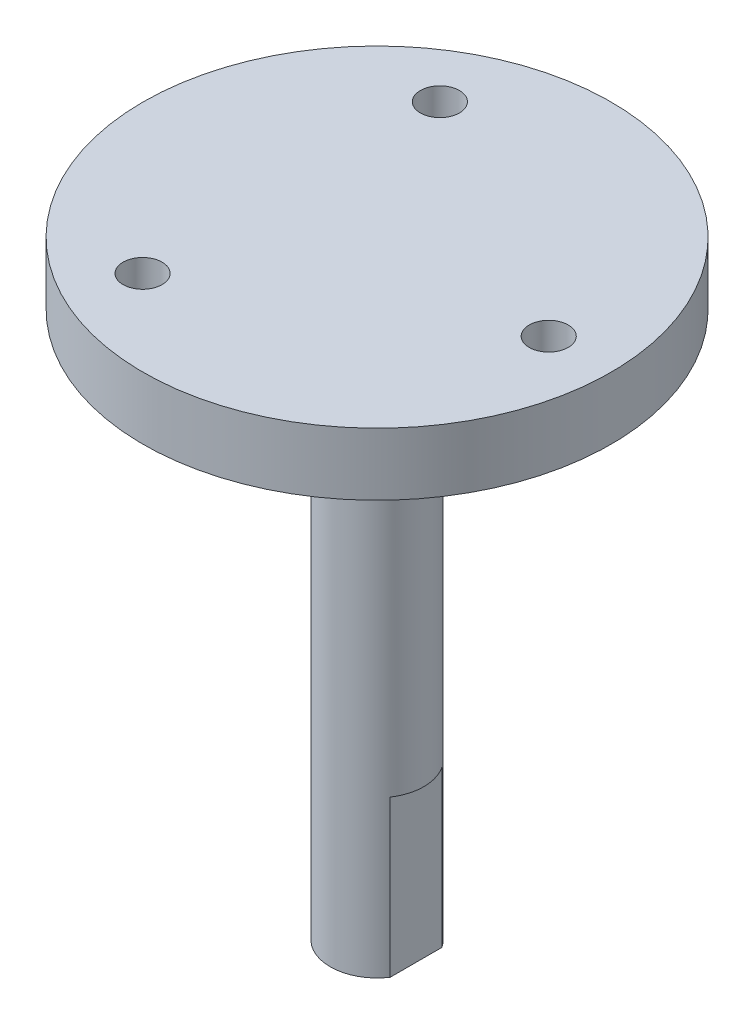
SolidWorks part; units mm, degrees
ref_plane "Alzado" through (0, 0, 0) normal (0, 0, 1) x (1, 0, 0)
ref_plane "Planta" through (0, 0, 0) normal (0, 1, 0) x (1, 0, 0)
ref_plane "Vista lateral" through (0, 0, 0) normal (1, 0, 0) x (0, 0, -1)
sketch "Croquis1" plane through (0, 0, 0) normal (0, 0, 1) x (1, 0, 0)
  line L0 (0, 0) -> (3, 0)
  line L5 (3, 0) -> (3, -39)
  line L6 (3, -39) -> (0, -39)
  line L7 (0, -39) -> (0, 0)
  line L8 (0, -39) -> (0, 5.7552) construction
  dimension "D3" = 39
  dimension "D7" = 6
revolve "Revolución1" add sketch "Croquis1" angle 360 about L8 region at (1.5, -19.5, 0)
sketch "Croquis2" plane through (0, -39, 0) normal (0, -1, 0) x (1, 0, 0)
  line L0 (2.5, 1.6583) -> (2.5, -1.6583)
  line L1 (0, 0) -> (3, 0) construction
  circle A0 centre (0, 0) radius 3
  circle A1 centre (0, 0) radius 3
  circle M3 centre (0, 0) radius 3
  dimension "D1" = 0.5
extrude "Cortar-Extruir1" cut sketch "Croquis2" against normal blind 10 contours L1 L0 M3 | L0 L1 A1 region at (2.7015, -39, 0.6294) region at (2.7015, -39, -0.6294)
sketch "Croquis4" plane through (0, 0, 0) normal (0, 1, 0) x (1, 0, 0)
  circle A2 centre (0, 0) radius 15
  dimension "D1" = 30
extrude "Saliente-Extruir1" add sketch "Croquis4" against normal blind 4
sketch "Croquis5" plane through (0, 0, 0) normal (0, 1, 0) x (1, 0, 0)
  line L0 (0, 0) -> (11, 0) construction
  point P0 (11, 0)
  point P5 (-5.5, -9.5263)
  point P8 (-5.5, 9.5263)
  point P9 (0, 0)
  dimension "D1" = 11
  dimension "D2" = 3
hole_wizard "Perforador para roscar para macho de roscar para M3x0.51" positions "Croquis5" profile "Croquis6" hole size "M3x0.5" standard "Ansi Metric" end condition up to next
sketch "Croquis6" plane through (11, 0, 0) normal (1, 0, 0) x (0, 0, 1)
  line L0 (0, 0) -> (0, 4)
  line L1 (0, 4) -> (1.25, 4)
  line L2 (1.25, 4) -> (1.25, 0)
  line L5 (1.25, 0) -> (0, 0)
  line L11 (0, -6.35) -> (0, 107.95) construction
  dimension "Diámetro de taladro hasta el siguiente" = 2.5
  dimension "Profundidad de taladro hasta el siguiente" = 4
cosmetic thread "Rosca cosmética1" parameters "D2"=3
cosmetic thread "Rosca cosmética2" parameters "D2"=3
cosmetic thread "Rosca cosmética3" parameters "D2"=3
cosmetic thread "Rosca cosmética4" parameters "D2"=3
equation "\"ParaTuerca\"= 20mm"
equation "\"gap\"= 2mm"
equation "\"ParMotor\"= 20mm"
equation "\"D1@Cortar-Extruir1\"=\"ParMotor\"-10"
